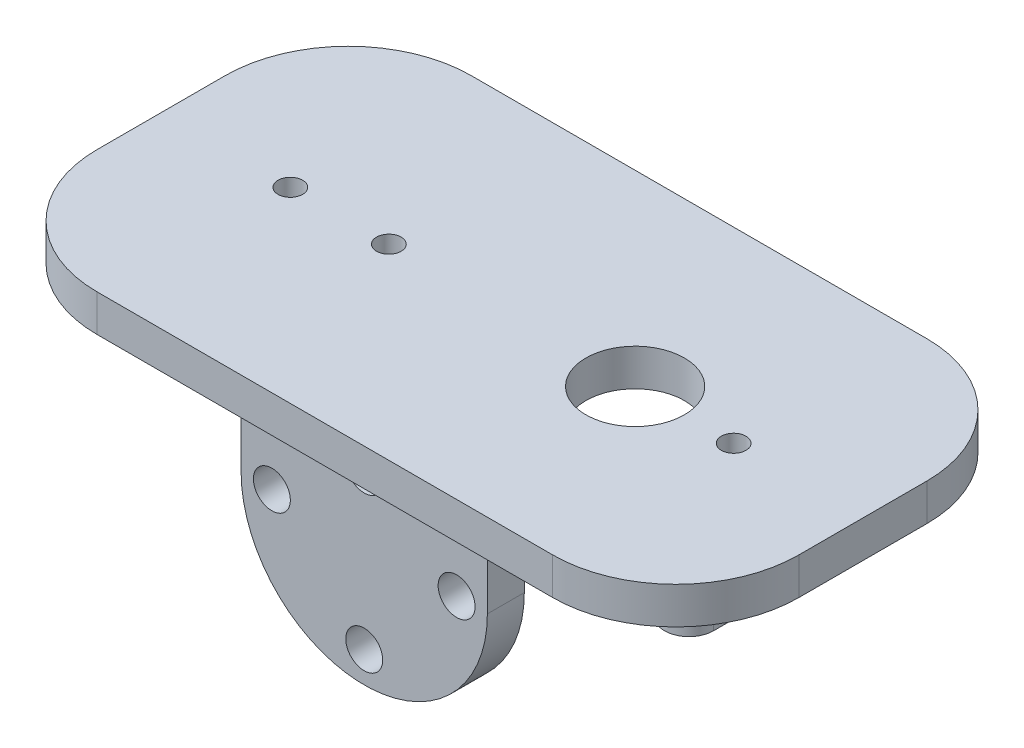
SolidWorks part; units mm, degrees
ref_plane "Front Plane" through (0, 0, 0) normal (0, 0, 1) x (1, 0, 0)
ref_plane "Top Plane" through (0, 0, 0) normal (0, 1, 0) x (1, 0, 0)
ref_plane "Right Plane" through (0, 0, 0) normal (1, 0, 0) x (0, 0, -1)
ref_plane "Plane1" through (0, 0, 0) normal (0, -1, 0) x (1, 0, 0)
sketch "Sketch1" plane through (0, 0, 0) normal (0, -1, 0) x (1, 0, 0)
  line L0 (28.5, 15.2) -> (-28.5, 15.2)
  line L1 (-28.5, 15.2) -> (-28.5, -15.2)
  line L2 (-28.5, -15.2) -> (28.5, -15.2)
  line L3 (28.5, -15.2) -> (28.5, 15.2)
  dimension "D1" = 57
extrude "Boss-Extrude1" add sketch "Sketch1" against normal blind 3
sketch "Sketch2" plane through (0, 0, 0) normal (0, -1, 0) x (1, 0, 0)
  line L0 (16.3736, -4) -> (16.3736, 4)
  line L1 (20.3736, 4) -> (20.3736, -4)
  arc A0 (20.3736, -4) -> (16.3736, -4) centre (18.3736, -4) cw
  arc A1 (16.3736, 4) -> (20.3736, 4) centre (18.3736, 4) cw
extrude "Boss-Extrude2" add sketch "Sketch2" along normal blind 7
ref_plane "Plane2" through (0, 0, 12) normal (0, 0, 1) x (1, 0, 0)
sketch "Sketch3" plane through (0, 0, 12) normal (0, 0, 1) x (1, 0, 0)
  line L0 (10, -7) -> (10, 0)
  line L1 (10, 0) -> (-10, 0)
  line L2 (-10, 0) -> (-10, -7)
  arc A0 (-10, -7) -> (10, -7) centre (0, -7) ccw
extrude "Boss-Extrude3" add sketch "Sketch3" against normal blind 3
sketch "Sketch4" plane through (0, 0, 0) normal (0, -1, 0) x (1, 0, 0)
  line L0 (-11.1264, -4) -> (-11.1264, 4)
  line L1 (-7.1264, 4) -> (-7.1264, -4)
  arc A0 (-7.1264, -4) -> (-11.1264, -4) centre (-9.1264, -4) cw
  arc A1 (-11.1264, 4) -> (-7.1264, 4) centre (-9.1264, 4) cw
extrude "Boss-Extrude4" add sketch "Sketch4" along normal blind 7
hole_wizard "Ø8.0 (8) Diameter Hole1" positions "Sketch6" profile "Sketch5" hole size "Ø8.0" standard "ANSI Metric"
sketch "Sketch6" plane through (0, 0, 0) normal (0, -1, 0) x (-1, 0, 0)
  point P0 (-10, 0)
sketch "Sketch5" plane through (10, 0, 0) normal (1, 0, 0) x (0, 0, -1)
  line L0 (0, 0) -> (0, 3)
  line L1 (0, 3) -> (4, 3)
  line L2 (4, 3) -> (4, 0)
  line L5 (4, 0) -> (0, 0)
  line L11 (0, -6.35) -> (0, 107.95) construction
  dimension "Thru Hole Dia." = 8
  dimension "Thru Hole Depth" = 3
hole_wizard "Ø2.0 (2) Diameter Hole1" positions "Sketch8" profile "Sketch7" hole size "Ø2.0" standard "ANSI Metric"
sketch "Sketch8" plane through (0, 0, 0) normal (0, -1, 0) x (-1, 0, 0)
  point P0 (18, 0)
sketch "Sketch7" plane through (-18, 0, 0) normal (1, 0, 0) x (0, 0, -1)
  line L0 (0, 0) -> (0, 3)
  line L1 (0, 3) -> (1, 3)
  line L2 (1, 3) -> (1, 0)
  line L5 (1, 0) -> (0, 0)
  line L11 (0, -6.35) -> (0, 107.95) construction
  dimension "Thru Hole Dia." = 2
  dimension "Thru Hole Depth" = 3
hole_wizard "Ø2.0 (2) Diameter Hole2" positions "Sketch10" profile "Sketch9" hole size "Ø2.0" standard "ANSI Metric"
sketch "Sketch10" plane through (0, 3, 0) normal (0, 1, 0) x (1, 0, 0)
  point P0 (18, 0)
  point P1 (-10, 0)
sketch "Sketch9" plane through (18, 3, 0) normal (1, 0, 0) x (0, 0, 1)
  line L0 (0, 0) -> (0, 3)
  line L1 (0, 3) -> (1, 3)
  line L2 (1, 3) -> (1, 0)
  line L5 (1, 0) -> (0, 0)
  line L10 (0, 3) -> (-1, 3) construction
  line L11 (0, -6.35) -> (0, 107.95) construction
  dimension "Hole Dia." = 2
  dimension "Hole Depth" = 3
  dimension "Drill Angle" = 180
hole_wizard "Ø3.0 (3) Diameter Hole1" positions "Sketch12" profile "Sketch11" hole size "Ø3.0" standard "ANSI Metric"
sketch "Sketch12" plane through (0, 0, 15.2) normal (0, 0, 1) x (1, 0, 0)
  point P0 (-7.5, -7)
sketch "Sketch11" plane through (-7.5, -7, 15.2) normal (1, 0, 0) x (0, -1, 0)
  line L0 (0, 0) -> (0, 6.2)
  line L1 (0, 6.2) -> (1.5, 6.2)
  line L2 (1.5, 6.2) -> (1.5, 0)
  line L5 (1.5, 0) -> (0, 0)
  line L11 (0, -6.35) -> (0, 107.95) construction
  dimension "Thru Hole Dia." = 3
  dimension "Thru Hole Depth" = 6.2
hole_wizard "Ø3.0 (3) Diameter Hole2" positions "Sketch14" profile "Sketch13" hole size "Ø3.0" standard "ANSI Metric"
sketch "Sketch14" plane through (0, 0, 15.2) normal (0, 0, 1) x (1, 0, 0)
  point P0 (0, -2)
  point P1 (7.5, -7)
  point P2 (0, -14.5)
sketch "Sketch13" plane through (0, -2, 15.2) normal (1, 0, 0) x (0, -1, 0)
  line L0 (0, 0) -> (0, 30.4)
  line L1 (0, 30.4) -> (1.5, 30.4)
  line L2 (1.5, 30.4) -> (1.5, 0)
  line L5 (1.5, 0) -> (0, 0)
  line L11 (0, -6.35) -> (0, 107.95) construction
  dimension "Thru Hole Dia." = 3
  dimension "Thru Hole Depth" = 30.4
hole_wizard "Ø2.0 (2) Diameter Hole3" positions "Sketch16" profile "Sketch15" hole size "Ø2.0" standard "ANSI Metric"
sketch "Sketch16" plane through (0, -7, 0) normal (0, -1, 0) x (-1, 0, 0)
  point P0 (-18.7492, -0.1146)
  point P1 (9.2483, 0.2522)
sketch "Sketch15" plane through (18.7492, -7, 0.1146) normal (1, 0, 0) x (0, 0, -1)
  line L0 (0, 0) -> (0, 5)
  line L1 (0, 5) -> (1, 5)
  line L2 (1, 5) -> (1, 0)
  line L5 (1, 0) -> (0, 0)
  line L10 (0, 5) -> (-1, 5) construction
  line L11 (0, -6.35) -> (0, 107.95) construction
  dimension "Hole Dia." = 2
  dimension "Hole Depth" = 5
  dimension "Drill Angle" = 180
fillet "Fillet1" radius 10 4 edges at (-28.5, 1.5, -15.2) (28.5, 1.5, -15.2) (-28.5, 1.5, 15.2) (28.5, 1.5, 15.2) tangent propagation no
split "Split1" bodies to split 112 resulting bodies 113 114 115 116 split by face at (-18, 0, -1)
